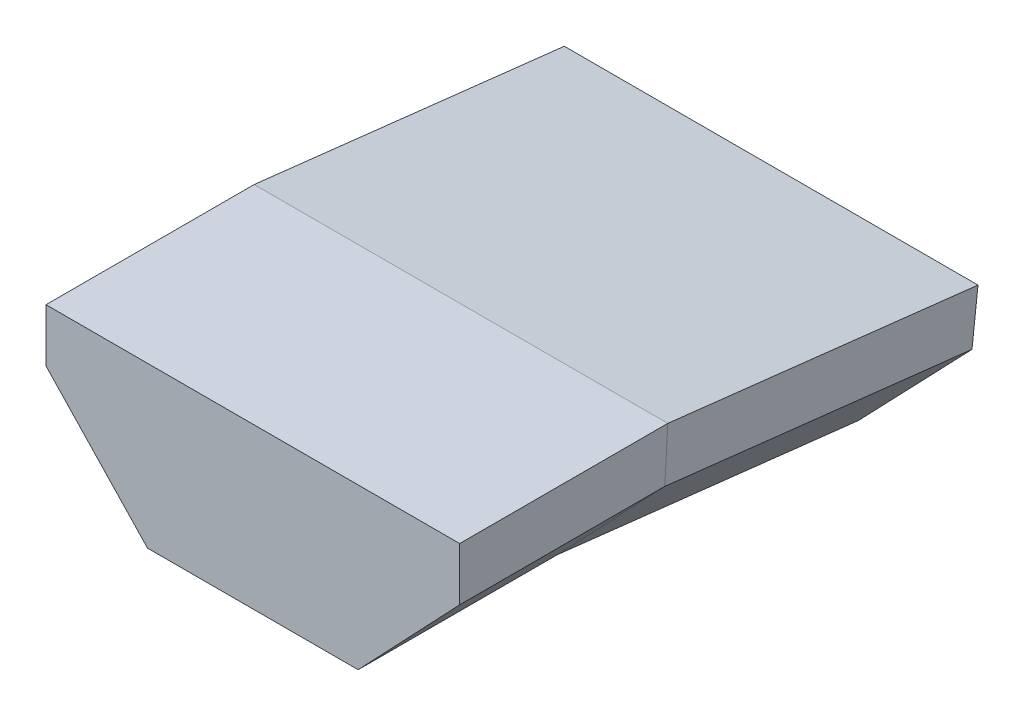
SolidWorks part; units mm, degrees
ref_plane "Front Plane" through (0, 0, 0) normal (0, 0, 1) x (1, 0, 0)
ref_plane "Top Plane" through (0, 0, 0) normal (0, 1, 0) x (1, 0, 0)
ref_plane "Right Plane" through (0, 0, 0) normal (1, 0, 0) x (0, 0, -1)
sketch "Sketch1" plane through (0, 0, 0) normal (0, 0, 1) x (1, 0, 0)
  line B0 (7.95, 0) -> (7.95, -2.04)
  line B1 (4.048, -6.1524) -> (-4.048, -6.1524)
  line B2 (-7.95, -2.04) -> (-7.95, 0)
  line B3 (-7.95, 0) -> (7.95, 0)
  line B4 (7.95, -2.04) -> (4.048, -6.1524)
  line B5 (-4.048, -6.1524) -> (-7.95, -2.04)
sketch_block_instance "Extrusion Profile-2"
sketch_block "Extrusion Profile" parameters "D1"=8.44, "D2"=2.6, "D3"=6, "D4"=16.7, "D6"=5.6686, "D7"=2.0404, "D8"=8.0963, "D9"=15.9, "D5"=2.4157
sketch "Sketch2" plane through (0, 0, 0) normal (1, 0, 0) x (0, 0, -1)
  line L0 (0, 0) -> (8, 0)
  line L1 (8, 0) -> (19.9229, -1.3584)
  dimension "D1" = 186.5
  dimension "D2" = 8
  dimension "D3" = 12
sweep "Sweep1" add profiles "Sketch1" path "Sketch2"
